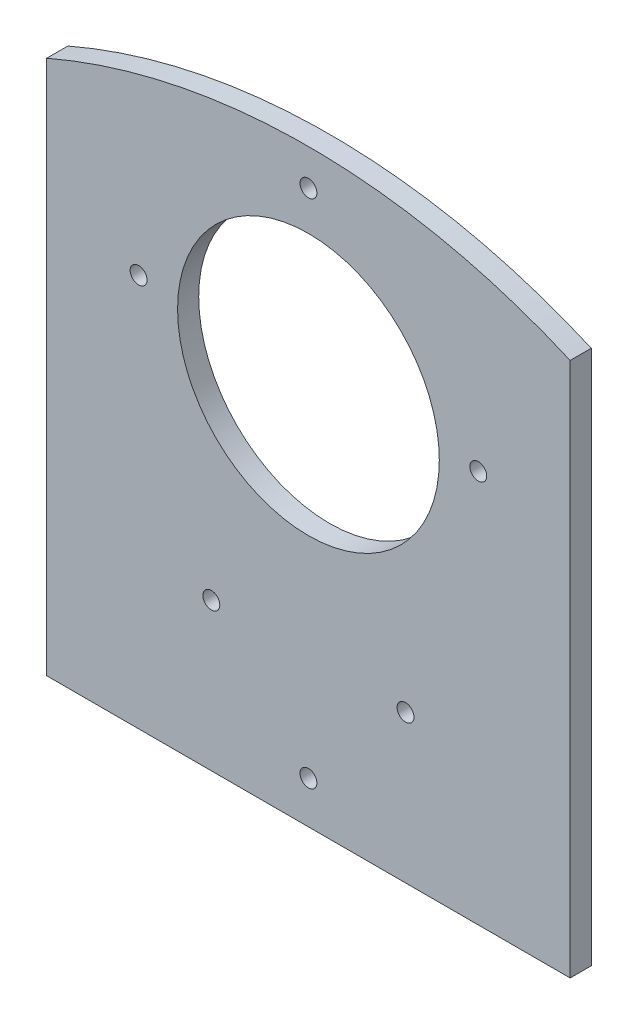
SolidWorks part; units mm, degrees
material "6061 Alloy"
ref_plane "Front Plane" through (0, 0, 0) normal (0, 0, 1) x (1, 0, 0)
ref_plane "Top Plane" through (0, 0, 0) normal (0, 1, 0) x (1, 0, 0)
ref_plane "Right Plane" through (0, 0, 0) normal (1, 0, 0) x (0, 0, -1)
sketch "Sketch1" plane through (0, 0, 0) normal (0, 0, 1) x (1, 0, 0)
  line L1 (35, -52.5) -> (-35, -52.5)
  line L2 (35, -52.5) -> (35, 52.5)
  line L3 (35, 52.5) -> (-35, 52.5)
  line L4 (-35, -52.5) -> (-35, 52.5)
  line L5 (35, -52.5) -> (-35, 52.5) construction
  line L6 (35, 52.5) -> (-35, -52.5) construction
  point P0 (0, 0)
  dimension "D1" = 70
  dimension "D2" = 105
extrude "Boss-Extrude1" add sketch "Sketch1" along normal blind 3
sketch "Sketch2" plane through (0, 0, 0) normal (0, 0, -1) x (-1, 0, 0)
  line L0 (-35, -2.5) -> (35, -2.5) construction
  line L1 (-35, -52.5) -> (-35, 52.5) construction
  line L2 (35, 52.5) -> (35, -52.5) construction
  line L3 (35, -52.5) -> (-35, -52.5) construction
  circle A0 centre (0, 20.5) radius 17.5
  point P11 (0, -2.5)
  dimension "D2" = 35
  dimension "D1" = 50
  dimension "D3" = 23
  dimension "D4" = 35
extrude "Cut-Extrude3" cut sketch "Sketch2" against normal blind 3 contours A0 region at (0, 20.5, 0)
sketch "Sketch3" plane through (0, 0, 3) normal (0, 0, 1) x (1, 0, 0)
  circle A5 centre (0, 20.5) radius 17.5 construction
  circle A6 centre (-22.5, 20.5) radius 2
  circle A7 centre (0, 43) radius 2
  circle A8 centre (22.5, 20.5) radius 2
  point P0 (0, 20.5)
  dimension "D2" = 22.5
  dimension "D3" = 22.5
  dimension "D4" = 4
  dimension "D5" = 4
  dimension "D6" = 4
  dimension "D1" = 22.5
sketch "Sketch4" plane through (0, 0, 3) normal (0, 0, 1) x (1, 0, 0)
  line L0 (0, 0) -> (0, -52.5) construction
  line L1 (-35, -52.5) -> (35, -52.5) construction
  circle A0 centre (0, -42.5) radius 2
  circle A1 centre (-23, -17.5) radius 2
  circle A3 centre (23, -17.5) radius 2
  dimension "D3" = 4
  dimension "D1" = 10
  dimension "D2" = 25
  dimension "D4" = 23
sketch "Sketch5" plane through (0, 0, 3) normal (0, 0, 1) x (1, 0, 0)
  line L0 (-35, 40.7935) -> (35, 40.7935) construction
  line L1 (-35, 52.5) -> (-35, -52.5) construction
  line L2 (35, -52.5) -> (35, 52.5) construction
  line L3 (-35, 40.7935) -> (-35, 52.5)
  line L4 (-35, 52.5) -> (35, 52.5)
  line L5 (35, 52.5) -> (35, 40.7935)
  arc A0 (-35, 40.7935) -> (35, 40.7935) centre (0, -39.6661) cw
extrude "Cut-Extrude6" cut sketch "Sketch5" against normal blind 10
scale "Scale1" scale about centroid uniform scaling yes scale factor 1.771429
ref_plane "Plane1" through (0, 0, -1.1571) normal (0, 0, -1) x (-1, 0, 0)
sketch "Sketch6" plane through (0, 0, -1.1571) normal (0, 0, -1) x (-1, 0, 0)
  line L3 (62, -87.3934) -> (62, 77.8695)
  line L4 (-62, 77.8695) -> (-62, -87.3934)
  line L5 (-62, -87.3934) -> (62, -87.3934)
  line L6 (62, -87.3934) -> (62, 77.8695)
  line L7 (-62, 77.8695) -> (-62, -87.3934)
  line L8 (-62, -87.3934) -> (62, -87.3934)
  circle A0 centre (0, 41.9209) radius 31 construction
  arc A1 (62, 77.8695) -> (-62, 77.8695) centre (0, -64.6591) ccw
  arc A2 (62, 77.8695) -> (-62, 77.8695) centre (0, -64.6591) ccw
  circle A3 centre (0, 41.9209) radius 31
  dimension "D1" = 0
extrude "Cut-Extrude7" cut sketch "Sketch6" against normal blind 0.31
sketch "Sketch7" plane through (0, 0, 4.1571) normal (0, 0, 1) x (1, 0, 0)
  line L0 (450, -48.8219) -> (-450, -48.8219) construction
  line L1 (62, -48.8219) -> (-62, -48.8219)
  line L2 (-62, -87.3934) -> (62, -87.3934) construction
  line L3 (-62, 77.8695) -> (-62, -87.3934) construction
  line L4 (62, -87.3934) -> (62, 77.8695) construction
  line L5 (-62, -87.3934) -> (62, -87.3934)
  line L6 (-62, -48.8219) -> (-62, -87.3934)
  line L7 (62, -87.3934) -> (62, -48.8219)
extrude "Cut-Extrude8" cut sketch "Sketch7" against normal blind 10
sketch "Sketch9" plane through (0, 0, 4.1571) normal (0, 0, 1) x (1, 0, 0)
  circle A0 centre (23, -13.8219) radius 2
  circle A1 centre (-23, -13.8219) radius 2
  circle A2 centre (0, -38.8219) radius 2
extrude "Cut-Extrude9" cut sketch "Sketch9" against normal up to surface (5.0043 mm away) up to face at (0, 17.7491, -0.8471)
sketch "Sketch10" plane through (0, 0, 4.1571) normal (0, 0, 1) x (1, 0, 0)
  circle A0 centre (-40.2334, 44.2368) radius 2
  circle A1 centre (0, 82.2209) radius 2
  circle A2 centre (40.2334, 44.2368) radius 2
extrude "Cut-Extrude10" cut sketch "Sketch10" against normal up to surface (5.0043 mm away) up to face at (21, -13.8219, -0.8471)
